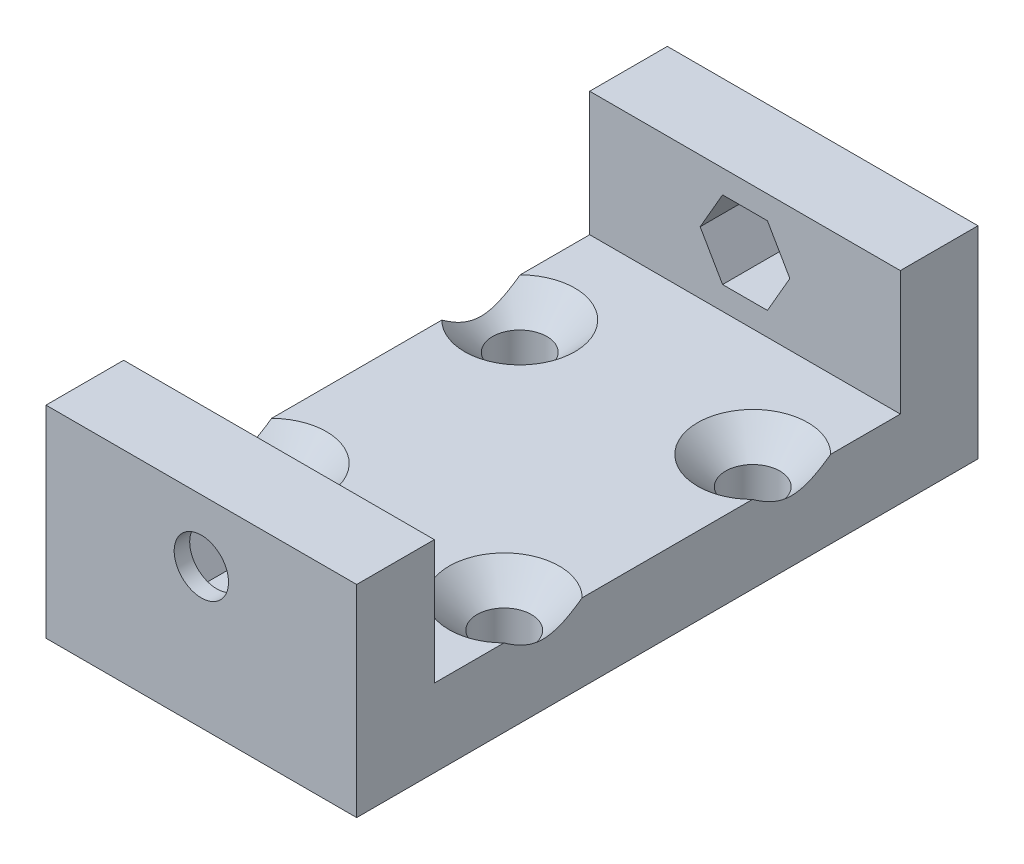
SolidWorks part; units mm, degrees
ref_plane "Front Plane" through (0, 0, 0) normal (0, 0, 1) x (1, 0, 0)
ref_plane "Top Plane" through (0, 0, 0) normal (0, 1, 0) x (1, 0, 0)
ref_plane "Right Plane" through (0, 0, 0) normal (1, 0, 0) x (0, 0, -1)
sketch "Sketch1" plane through (0, 0, 0) normal (0, 1, 0) x (1, 0, 0)
  line L1 (-10, 20) -> (10, 20)
  line L2 (-10, 20) -> (-10, -20)
  line L3 (-10, -20) -> (10, -20)
  line L4 (10, 20) -> (10, -20)
  line L5 (-10, 20) -> (10, -20) construction
  line L6 (-10, -20) -> (10, 20) construction
  line L7 (-7.5, -8) -> (7.5, -8) construction
  line L8 (-7.5, -8) -> (-7.5, 8) construction
  line L9 (-7.5, 8) -> (7.5, 8) construction
  line L10 (7.5, -8) -> (7.5, 8) construction
  line L11 (-7.5, -8) -> (7.5, 8) construction
  line L12 (-7.5, 8) -> (7.5, -8) construction
  circle A0 centre (-7.5, 8) radius 1.75
  circle A1 centre (-7.5, -8) radius 1.75
  circle A2 centre (7.5, -8) radius 1.75
  circle A3 centre (7.5, 8) radius 1.75
  point P0 (0, 0)
  point P5 (0, 0)
  dimension "D5" = 3.5
  dimension "D6" = 3.5
  dimension "D1" = 40
  dimension "D2" = 20
  dimension "D3" = 15
  dimension "D4" = 16
extrude "Boss-Extrude1" add sketch "Sketch1" along normal blind 5
sketch "Sketch2" plane through (0, 5, 0) normal (0, 1, 0) x (1, 0, 0)
  line L0 (10, -20) -> (10, 20) construction
  line L1 (-10, 20) -> (10, 20)
  line L2 (-10, 20) -> (-10, 15)
  line L3 (-10, 15) -> (10, 15)
  line L4 (10, 20) -> (10, 15)
  line L6 (-10, -20) -> (10, -20)
  line L7 (-10, -20) -> (-10, -15)
  line L8 (-10, -15) -> (10, -15)
  line L9 (10, -20) -> (10, -15)
  dimension "D1" = 5
extrude "Boss-Extrude2" add sketch "Sketch2" along normal blind 8
sketch "Sketch3" plane through (0, 0, -20) normal (0, 0, -1) x (-1, 0, 0)
  line L0 (0, 13) -> (0, 5) construction
  line L1 (-10, 13) -> (10, 13) construction
  line L2 (10, 5) -> (-10, 5) construction
  circle A0 centre (0, 9) radius 1.75
  dimension "D2" = 3.5
extrude "Cut-Extrude1" cut sketch "Sketch3" against normal through all
sketch "Sketch4" plane through (0, 0, -15) normal (0, 0, 1) x (1, 0, 0)
  line L1 (-2.8868, 9) -> (-1.4434, 6.5)
  line L2 (-1.4434, 6.5) -> (1.4434, 6.5)
  line L3 (1.4434, 6.5) -> (2.8868, 9)
  line L4 (2.8868, 9) -> (1.4434, 11.5)
  line L5 (1.4434, 11.5) -> (-1.4434, 11.5)
  line L6 (-1.4434, 11.5) -> (-2.8868, 9)
  circle A0 centre (0, 9) radius 2.5 construction
  dimension "D1" = 5
extrude "Cut-Extrude2" cut sketch "Sketch4" against normal blind 4
mirror "Mirror1" about plane through (0, 0, 0) normal (0, 0, 1) of "Cut-Extrude2"
chamfer "Chamfer1" distance 1.8 angle 45 4 edges at (-7.5, 5, 9.75) (7.5, 5, 9.75) (7.5, 5, -6.25) (-7.5, 5, -6.25)
